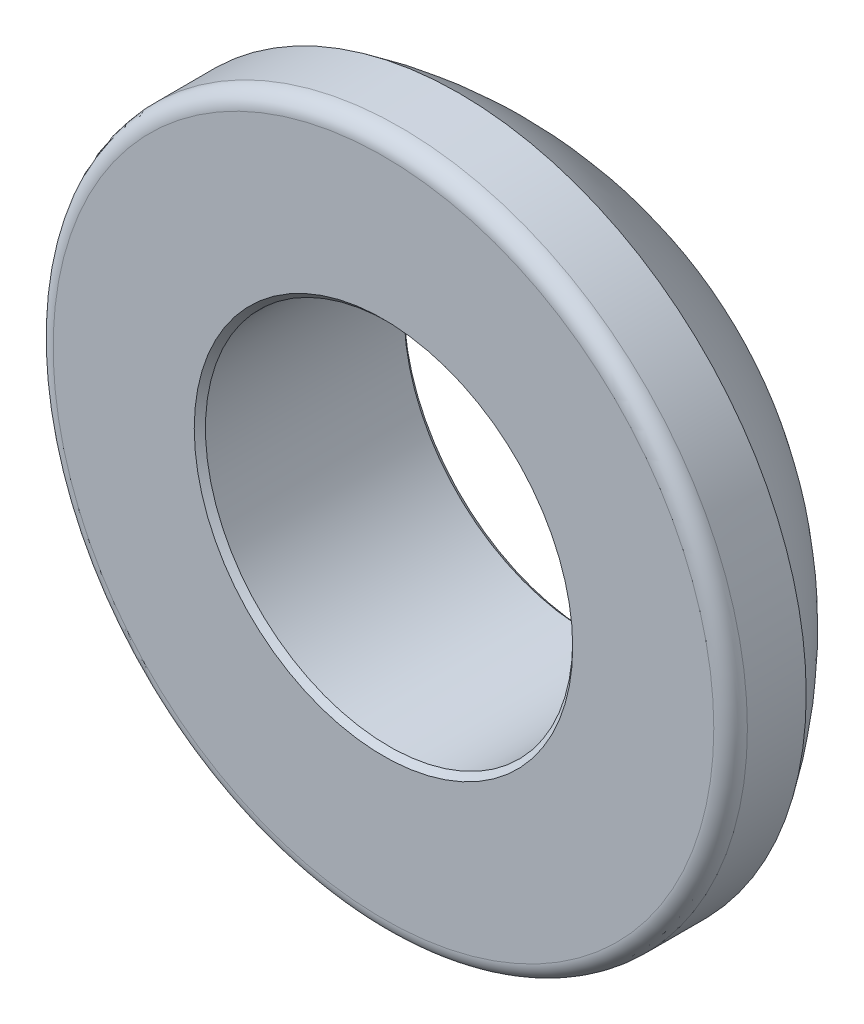
SolidWorks part; units mm, degrees
ref_plane "front" through (0, 0, 0) normal (0, 0, 1) x (1, 0, 0)
ref_plane "top" through (0, 0, 0) normal (0, 1, 0) x (1, 0, 0)
ref_plane "right" through (0, 0, 0) normal (1, 0, 0) x (0, 0, -1)
sketch "Sketch1" plane through (0, 0, 0) normal (1, 0, 0) x (0, 0, -1)
  line L0 (9.271, 8.3312) -> (9.525, 8.5852)
  line L1 (9.525, 8.5852) -> (9.525, 9.1092)
  line L2 (0, 8.5852) -> (0, 14.986)
  line L3 (0.762, 15.748) -> (3.4307, 15.748)
  line L4 (32.6431, 0) -> (56.1513, 0) construction
  line L5 (0.254, 8.3312) -> (9.271, 8.3312)
  line L6 (0, 8.5852) -> (0.254, 8.3312)
  arc A0 (9.525, 9.1092) -> (3.4307, 15.748) centre (-7.0612, 0) ccw
  arc A1 (0.762, 15.748) -> (0, 14.986) centre (0.762, 14.986) ccw
  point P4 (0, 15.748)
  dimension "D1" = 18.923
  dimension "D10" = 0.762
  dimension "D2" = 9.525
  dimension "D4" = 31.496
  dimension "D5" = 16.6624
  dimension "D6" = 17.1704
  dimension "D7" = 45
  dimension "D8" = 17.1704
  dimension "D9" = 45
  dimension "D11" = 2.6687
  dimension "D12" = 16.5862
revolve "Revolve1" add sketch "Sketch1" angle 360 about L4
ref_axis "Axis1" through (0, 0, -24.9432) along (0, 0, 1)
